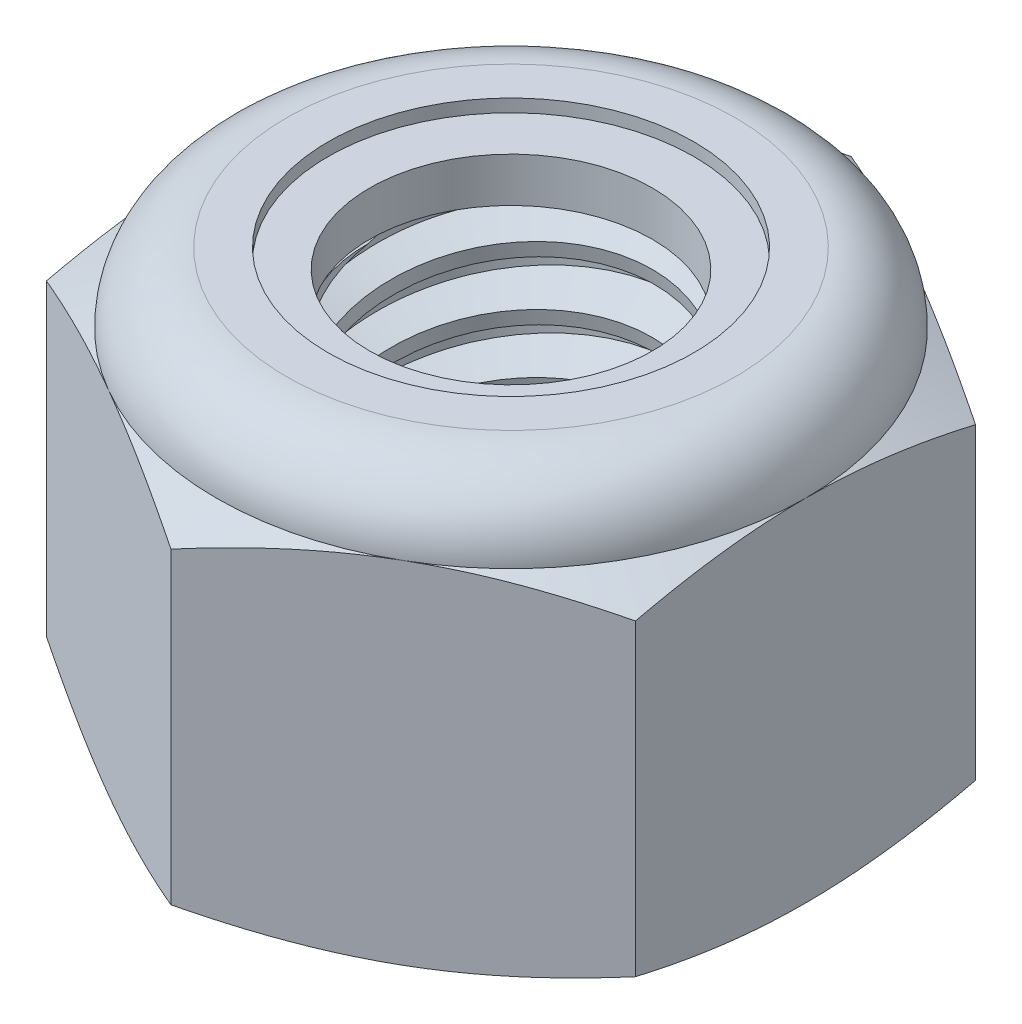
SolidWorks part; units mm, degrees
ref_plane "Front" through (0, 0, 0) normal (0, 0, 1) x (1, 0, 0)
ref_plane "Top" through (0, 0, 0) normal (0, 1, 0) x (1, 0, 0)
ref_plane "Right" through (0, 0, 0) normal (1, 0, 0) x (0, 0, -1)
sketch "Sketch1" plane through (0, 0, 0) normal (0, 1, 0) x (1, 0, 0)
  line L1 (0, 4.0415) -> (-3.5, 2.0207)
  line L2 (-3.5, 2.0207) -> (-3.5, -2.0207)
  line L3 (-3.5, -2.0207) -> (0, -4.0415)
  line L4 (0, -4.0415) -> (3.5, -2.0207)
  line L5 (3.5, -2.0207) -> (3.5, 2.0207)
  line L6 (3.5, 2.0207) -> (0, 4.0415)
  circle A0 centre (0, 0) radius 3.5 construction
  dimension "Hex Flats" = 7
extrude "Extrude1" add sketch "Sketch1" along normal blind 5
sketch "Sketch2" plane through (0, 0, 0) normal (1, 0, 0) x (0, 0, -1)
  line L0 (-2, 0) -> (-2, 5) construction
  line L1 (0, 0) -> (2, 0)
  line L2 (0, 0) -> (0, 5)
  line L3 (0, 5) -> (2, 5)
  line L4 (2, 0) -> (2, 5)
  line L5 (-2.0207, 5) -> (2.0207, 5) construction
  line L7 (0, -2) -> (0, 0) construction
  dimension "Thread Dia" = 4
revolve "Revolve1" add sketch "Sketch2" angle 360 about L7
sketch "Sketch3" plane through (0, 0, 0) normal (1, 0, 0) x (0, 0, -1)
  line L0 (2, 5) -> (-2, 5) construction
  line L1 (-2, 5) -> (-2, 4.3) construction
  line L2 (-2, 4.3) -> (2, 5) construction
  line L3 (2, 5) -> (2.0151, 4.9138) construction
  line L4 (2.0151, 4.9138) -> (2.1207, 4.3105)
  line L5 (2.1207, 4.3105) -> (1.7097, 4.4606)
  line L6 (1.7097, 4.4606) -> (1.6796, 4.633)
  line L7 (1.6796, 4.633) -> (2.0151, 4.9138)
  line L8 (1.6947, 4.5468) -> (2.0679, 4.6121) construction
  line L9 (2, 5) -> (2, 4.6003) construction
  line L10 (2, 4.6003) -> (-2, 3.9003) construction
  line L11 (-2, 3.9003) -> (-2, 4.3) construction
  line L12 (-0.1312, 5) -> (0.1312, 3.5005) construction
  line L13 (-2, 0) -> (-2, 5) construction
  line L14 (0, 5) -> (2, 5) construction
  line L15 (2, 0) -> (2, 5) construction
  point P13 (0, 4.2503)
  dimension "D1" = 0.0875
  dimension "D2" = 0.175
  dimension "Thread Pitch" = 0.7
  dimension "D4" = 60
  dimension "D5" = 0.7
revolve "Cut-Revolve1" cut sketch "Sketch3" angle 360 about L12
pattern_linear "LPattern1" count 7 spacing 0.7 along (0, -1, 0) count 2 spacing 0.7 along (0, 1, 0) of "Cut-Revolve1"
sketch "Sketch4" plane through (0, 0, 0) normal (1, 0, 0) x (0, 0, -1)
  line L0 (0, 5) -> (2, 5)
  line L1 (2, 5) -> (1.6796, 4.8506)
  line L2 (1.6796, 4.8506) -> (1.6796, 0.1494)
  line L3 (1.6796, 0.1494) -> (2, 0)
  line L4 (2, 0) -> (0, 0)
  line L5 (0, 0) -> (0, 5)
  line L6 (2, 0) -> (2, 5) construction
  line L7 (0, 5) -> (2, 5) construction
  line L8 (0, 0) -> (2, 0) construction
  line L9 (0, 0) -> (0, 5) construction
  line L10 (0, 5) -> (0, 5.3535) construction
  dimension "D1" = 25
revolve "Cut-Revolve2" cut sketch "Sketch4" angle 360 about L10
combine bodies "Combine1" operation type subtract main body 112 bodies to subtract 111
sketch "Sketch5" plane through (0, 0, 0) normal (1, 0, 0) x (0, 0, -1)
  line L0 (0, 0) -> (3.5, 0)
  line L1 (3.5, 0) -> (4.0415, 0.2525)
  line L2 (4.0415, 0.2525) -> (4.0415, 3.9142)
  line L3 (4.0415, 3.9142) -> (3.5, 4.1667)
  line L4 (2.6667, 5) -> (2.6667, 6.27)
  line L5 (2.6667, 6.27) -> (5.3115, 6.27)
  line L6 (5.3115, 6.27) -> (5.3115, -1.27)
  line L7 (5.3115, -1.27) -> (0, -1.27)
  line L8 (0, -1.27) -> (0, 0)
  line L9 (3.5, 4.1667) -> (3.5, 0) construction
  line L10 (0, 0) -> (2, 0) construction
  line L13 (4.0415, 2.0833) -> (5.3115, 2.0833) construction
  line L14 (4.0415, 5) -> (4.0415, 0) construction
  line L15 (0, 0) -> (0, 6.27) construction
  line L20 (0, 6.27) -> (2.6667, 6.27) construction
  line L22 (0, 5) -> (2, 5) construction
  arc A0 (3.5, 4.1667) -> (2.6667, 5) centre (2.6667, 4.1667) ccw
  dimension "D1" = 25
  dimension "D2" = 1.27
  dimension "D3" = 5
  dimension "D4" = 0.8333
revolve "Cut-Revolve3" cut sketch "Sketch5" angle 360 about L15
sketch "Sketch6" plane through (0, 0, 0) normal (1, 0, 0) x (0, 0, -1)
  line L0 (0, 4.1667) -> (3.3476, 4.1667)
  line L1 (2.6667, 4.8476) -> (2.1731, 4.8476)
  line L2 (0, 6.27) -> (0, 4.1667)
  line L3 (2.1731, 6.27) -> (0, 6.27)
  line L4 (0, 6.27) -> (2.6667, 6.27) construction
  line L5 (0, 0) -> (0, 6.27) construction
  line L6 (0, 6.27) -> (0, 44.323) construction
  line L7 (2.1731, 4.8476) -> (2.1731, 6.27)
  line L8 (2.6667, 5) -> (2.6667, 4.8476) construction
  line L9 (2.1731, 4.8476) -> (1.6796, 4.8476) construction
  line L10 (1.6796, 4.8476) -> (1.6796, 4.8506) construction
  arc A0 (3.3476, 4.1667) -> (2.6667, 4.8476) centre (2.6667, 4.1667) ccw
  arc A1 (3.5, 4.1667) -> (2.6667, 5) centre (2.6667, 4.1667) ccw construction
  dimension "D1" = 0.1524
revolve "Cut-Revolve4" cut sketch "Sketch6" angle 360 about L6
sketch "Sketch7" plane through (0, 0, 0) normal (1, 0, 0) x (0, 0, -1)
  line L0 (1.6796, 4.2429) -> (3.2666, 4.2429)
  line L1 (2.6667, 4.7714) -> (1.6796, 4.7714)
  line L2 (1.6796, 4.7714) -> (1.6796, 4.2429)
  line L3 (1.6796, 4.2429) -> (0, 4.2429) construction
  line L4 (0, 4.2429) -> (0, 4.7714) construction
  line L5 (0, 4.7714) -> (1.6796, 4.7714) construction
  line L6 (1.6796, 4.2429) -> (1.6796, 4.1667) construction
  line L7 (0, 4.1667) -> (3.3476, 4.1667) construction
  line L8 (2.6667, 4.7714) -> (2.6667, 4.8476) construction
  arc A0 (3.2666, 4.2429) -> (2.6667, 4.7714) centre (2.6667, 4.1667) ccw
  arc A2 (3.3476, 4.1667) -> (2.6667, 4.8476) centre (2.6667, 4.1667) ccw construction
  dimension "D1" = 0.0762
revolve "Revolve2" add sketch "Sketch7" angle 360 about L4
equation "\"D1@Sketch3\"=\"Thread Pitch@Sketch3\"/8"
equation "\"D2@Sketch3\"=\"Thread Pitch@Sketch3\"/4"
equation "\"D5@Sketch3\"=\"Thread Pitch@Sketch3\""
equation "\"D4@LPattern1\"=\"Thread Pitch@Sketch3\""
equation "\"D3@LPattern1\"=\"Thread Pitch@Sketch3\""
equation "\"D1@LPattern1\"=\"Height@Extrude1\"/\"Thread Pitch@Sketch3\""
equation "\"D4@Sketch5\"=\"Height@Extrude1\"/6"
